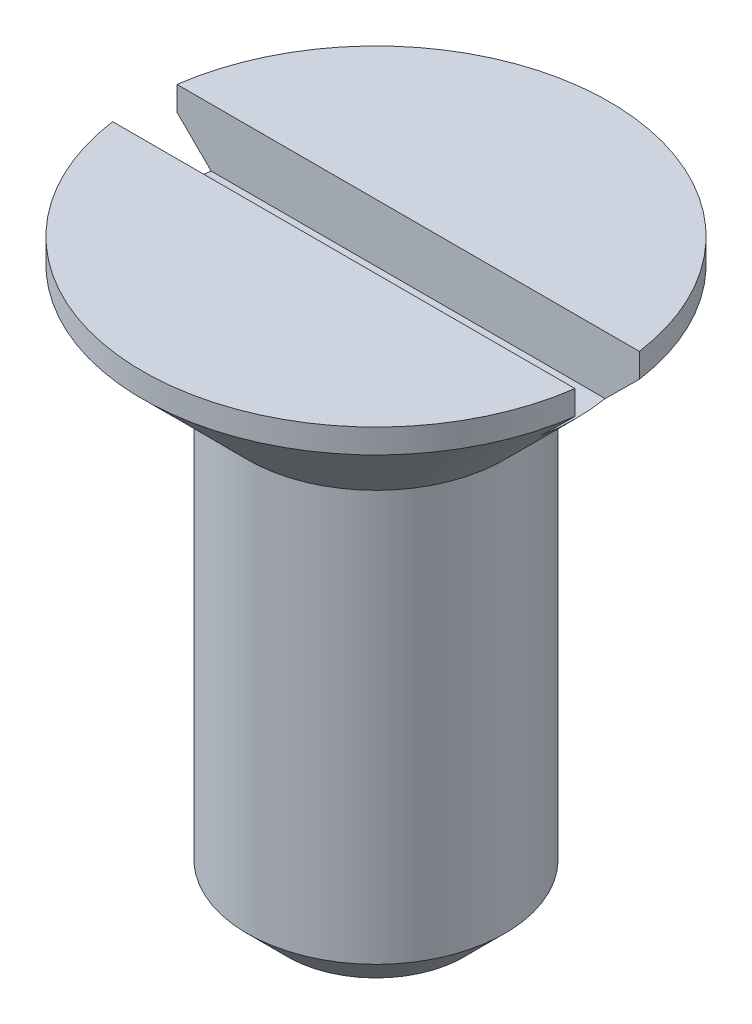
SolidWorks part; units mm, degrees
ref_plane "Спереди" through (0, 0, 0) normal (0, 0, 1) x (1, 0, 0)
ref_plane "Сверху" through (0, 0, 0) normal (0, 1, 0) x (1, 0, 0)
ref_plane "Справа" through (0, 0, 0) normal (1, 0, 0) x (0, 0, -1)
sketch "Эскиз1" plane through (0, 0, 0) normal (0, 0, 1) x (1, 0, 0)
  line L0 (0, 125.7632) -> (0, 0) construction
  line L2 (0, 92.035) -> (0, 74.035)
  line L3 (0, 92.035) -> (7.25, 92.035)
  line L4 (4, 88.035) -> (4, 74.035)
  line L5 (4, 88.035) -> (7.25, 91.285)
  line L6 (4, 74.035) -> (0, 74.035)
  line L7 (7.25, 92.035) -> (7.25, 91.285)
  dimension "D1" = 7.25
  dimension "D2" = 18
  dimension "D3" = 4
  dimension "D5" = 4
revolve "Повернуть1" add sketch "Эскиз1" angle 360 about L0
ref_axis "Ось4" through (0, 6.767, 0) along (0, -1, 0)
sketch "Эскиз13" plane through (0, 92.035, 0) normal (0, 1, 0) x (-1, 0, 0)
  line L1 (7.25, -1) -> (-7.25, -1)
  line L2 (7.25, -1) -> (7.25, 1)
  line L3 (7.25, 1) -> (-7.25, 1)
  line L4 (-7.25, -1) -> (-7.25, 1)
  dimension "D1" = 7.25
  dimension "D2" = 14.5
  dimension "D3" = 1
  dimension "D4" = 2
extrude "Вырез-Вытянуть9" cut sketch "Эскиз13" against normal blind 1.8
chamfer "Фаска1" distance 1.25 angle 45 1 edges at (-4, 74.035, 0)
